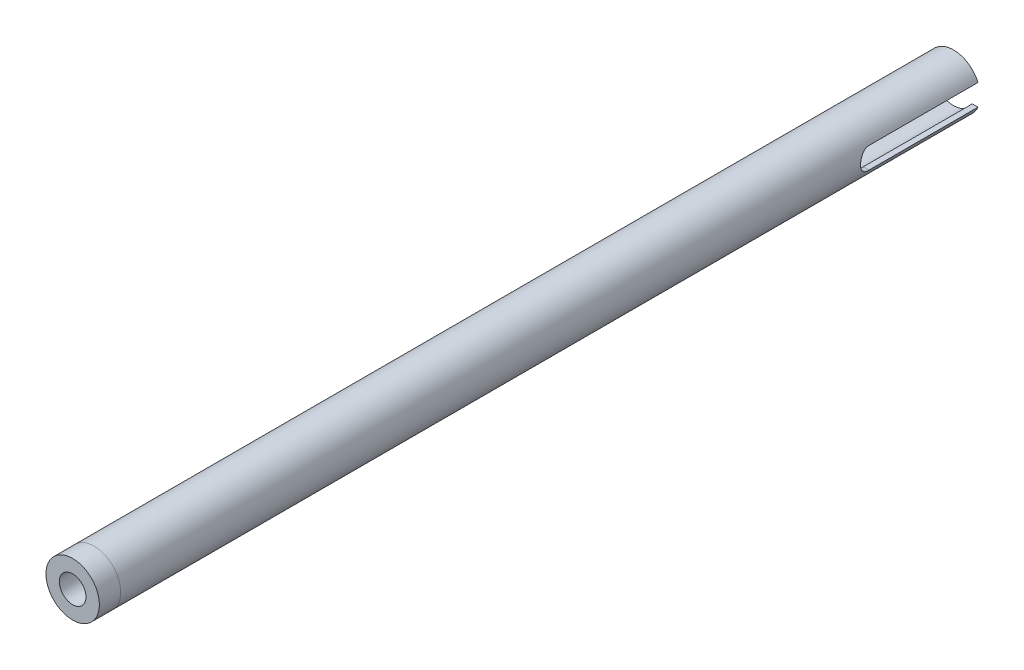
SolidWorks part; units mm, degrees
material "AISI 4130 Steel, annealed at 865C"
ref_plane "Front Plane" through (0, 0, 0) normal (0, 0, 1) x (1, 0, 0)
ref_plane "Top Plane" through (0, 0, 0) normal (0, 1, 0) x (1, 0, 0)
ref_plane "Right Plane" through (0, 0, 0) normal (1, 0, 0) x (0, 0, -1)
sketch "Axis" plane through (0, 0, 0) normal (0, 1, 0) x (1, 0, 0)
  line L0 (0, 0) -> (0, 261.7964) construction
  line L1 (0, 0) -> (0, -34.925) construction
  line L2 (0, 261.7964) -> (-7.9375, 261.7964) construction
  line L4 (0, 285.2197) -> (-10.3188, 254.7694) construction
  dimension "D1" = 34.925
  dimension "D2" = 7.9375
sketch "Sketch1" plane through (0, 0, 0) normal (0, 0, 1) x (1, 0, 0)
  line L0 (-7.9375, 0) -> (7.9375, 0) construction
  line L1 (-7.2748, 3.175) -> (7.2748, 3.175)
  line L2 (-7.2748, -3.175) -> (7.2748, -3.175)
  circle A0 centre (0, 0) radius 7.9375
  circle A1 centre (0, 0) radius 6.4135
  circle A2 centre (0, 0) radius 3.9688
  dimension "D1" = 15.875
  dimension "D3" = 7.9375
  dimension "D2" = 1.524
  dimension "D4" = 6.35
extrude "Threaded insert 1-1" add sketch "Sketch1" against normal blind 6.35 contours A2 L1 A1 | A1 L1 A0 | A2 L0 A1 L1 | A1 L0 A0 L1 | L0 A1 L2 A0 | L0 A2 L2 A1 | A2 L2 A1 | A1 L2 A0 | L0 A1 L2 A2 | L0 A0 L2 A1 | A0 L0 A1 L1 | A1 L0 A2 L1 region at (4.7887, 1.6543, 0) region at (4.7887, -1.6543, 0) region at (6.9234, 1.6163, 0) region at (6.9234, -1.6163, 0) region at (-4.7887, -1.6543, 0) region at (-4.7887, 1.6543, 0) region at (0, 4.6159, 0) region at (0, -4.6159, 0) region at (0, 6.5666, 0) region at (6.4237, -3.3281, 0) region at (-6.9234, -1.6163, 0) region at (-6.9234, 1.6163, 0)
extrude "Threaded insert 1-2" add sketch "Sketch1<3>" against normal blind 9.525 from surface contours A2 L1 A1 | A2 L0 A1 L1 | L0 A2 L2 A1 | A2 L2 A1 | L0 A1 L2 A2 | A1 L0 A2 L1 region at (4.7887, 1.6543, 0) region at (4.7887, -1.6543, 0) region at (-4.7887, -1.6543, 0) region at (-4.7887, 1.6543, 0) region at (0, 4.6159, 0) region at (0, -4.6159, 0) starting at face at (7.9375, 0, -6.35)
sketch "Sketch1<3>" plane through (0, 0, 0) normal (0, 0, 1) x (1, 0, 0) same geometry as "Sketch1"
extrude "A-arm tube" add sketch "Sketch1<4>" against normal up to vertex (261.7964 mm away) from surface separate body contours A1 L1 A0 | A1 L0 A0 L1 | L0 A1 L2 A0 | A1 L2 A0 | L0 A0 L2 A1 | A0 L0 A1 L1 region at (6.9234, 1.6163, 0) region at (6.9234, -1.6163, 0) region at (0, 6.5666, 0) region at (6.4237, -3.3281, 0) region at (-6.9234, -1.6163, 0) region at (-6.9234, 1.6163, 0) up to point (0, 0, -261.7964) starting at face at (6.4135, 0, -6.35)
sketch "Sketch1<4>" plane through (0, 0, 0) normal (0, 0, 1) x (1, 0, 0) same geometry as "Sketch1"
extrude "Apex slot" cut sketch "Sketch1<5>" along normal blind 35.56 from surface contours A0 L0 A1 L1 | L0 A0 L2 A1 | A1 L0 A0 L1 | L0 A1 L2 A0 region at (6.9234, 1.6163, 0) region at (6.9234, -1.6163, 0) region at (-6.9234, -1.6163, 0) region at (-6.9234, 1.6163, 0) starting at face at (6.4135, 0, -261.7964)
sketch "Sketch1<5>" plane through (0, 0, 0) normal (0, 0, 1) x (1, 0, 0) same geometry as "Sketch1"
fillet "Fillet1" radius 3.175 4 edges at (-6.4237, 3.175, -226.2364) (-6.4237, -3.175, -226.2364) (6.4237, -3.175, -226.2364) (6.4237, 3.175, -226.2364)
equation "\"tube diameter\"= 5 / 8"
equation "\"tube thickness\"= .06"
equation "\"apex thickness\"= .25"
equation "\"tube slot\"= 1.4"
equation "\"D1@Sketch1\"=\"tube diameter\""
equation "\"D2@Sketch1\"=\"tube thickness\""
equation "\"threaded insert hole\"= .3125"
equation "\"D3@Sketch1\"=\"threaded insert hole\""
equation "\"D4@Sketch1\"=\"apex thickness\""
equation "\"D1@Apex slot\" = \"tube slot\""
equation "\"D1@Fillet1\"=\"apex thickness\"/2"
